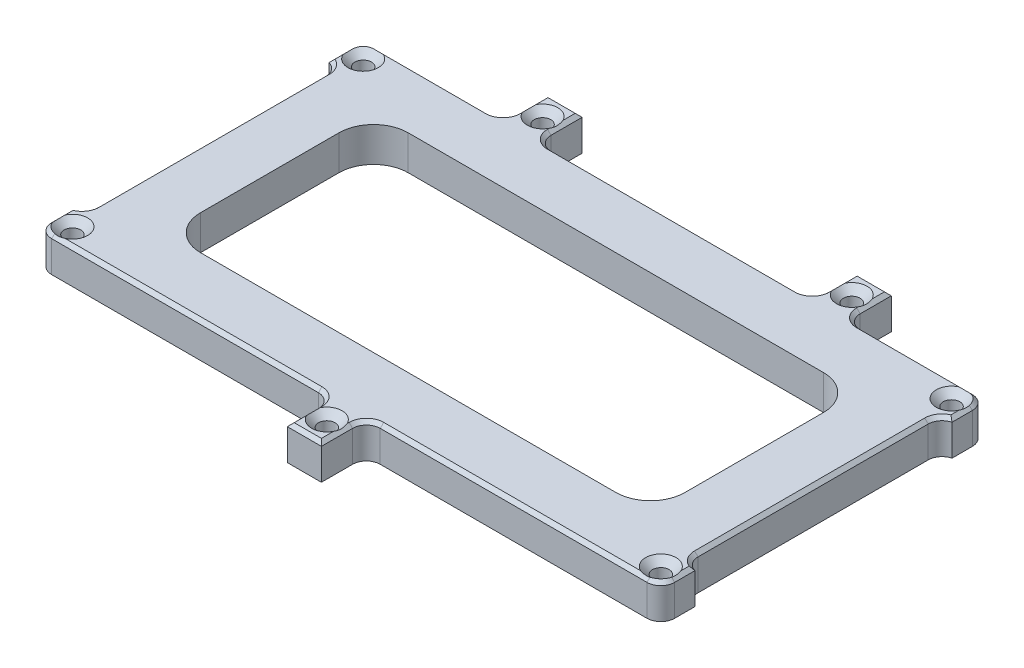
SolidWorks part; units mm, degrees
material "ABS"
ref_plane "Front Plane" through (0, 0, 0) normal (0, 0, 1) x (1, 0, 0)
ref_plane "Top Plane" through (0, 0, 0) normal (0, 1, 0) x (1, 0, 0)
ref_plane "Right Plane" through (0, 0, 0) normal (1, 0, 0) x (0, 0, -1)
sketch "Sketch1" plane through (0, 0, 0) normal (0, 1, 0) x (1, 0, 0)
  line L0 (-45, -23.5) -> (-45, -18.565)
  line L5 (-45, -23.5) -> (45, -23.5) construction
  line L6 (-45, -23.5) -> (-45, 23.5) construction
  line L7 (-45, 23.5) -> (45, 23.5) construction
  line L8 (45, -23.5) -> (45, 23.5) construction
  line L9 (-45, -23.5) -> (45, 23.5) construction
  line L10 (-45, 23.5) -> (45, -23.5) construction
  line L11 (-45, -18.565) -> (-43.5, -18.565)
  line L12 (-43.5, -18.565) -> (-43.5, 18.565)
  line L13 (-43.5, 18.565) -> (-45, 18.565)
  line L14 (-45, 18.565) -> (-45, 23.5)
  line L15 (-45, 23.5) -> (-24.8, 23.5)
  line L16 (-24.8, 23.5) -> (-24.8, 30)
  line L17 (-24.8, 30) -> (-19.87, 30)
  line L18 (-19.87, 30) -> (-19.87, 23.5)
  line L19 (-19.87, 23.5) -> (19.87, 23.5)
  line L20 (19.87, 23.5) -> (19.87, 30)
  line L21 (19.87, 30) -> (24.8, 30)
  line L22 (24.8, 30) -> (24.8, 23.5)
  line L23 (24.8, 23.5) -> (45, 23.5)
  line L24 (45, 23.5) -> (45, 18.565)
  line L25 (45, 18.565) -> (43.5, 18.565)
  line L26 (43.5, 18.565) -> (43.5, -18.565)
  line L27 (43.5, -18.565) -> (45, -18.565)
  line L28 (45, -18.565) -> (45, -23.5)
  line L29 (45, -23.5) -> (2.465, -23.5)
  line L30 (2.465, -23.5) -> (2.465, -30)
  line L31 (2.465, -30) -> (-2.465, -30)
  line L32 (-2.465, -30) -> (-2.465, -23.5)
  line L33 (-2.465, -23.5) -> (-45, -23.5)
  point P0 (0, 0)
  dimension "D1" = 47
  dimension "D2" = 90
  dimension "D3" = 87
  dimension "D4" = 60
  dimension "D5" = 20.2
  dimension "D6" = 4.93
  dimension "D7" = 37.13
extrude "Boss-Extrude1" add sketch "Sketch1" along normal blind 5
hole_wizard "CSK for M2 Countersunk Flat Head Screw1" positions "Sketch2" profile "Sketch3" countersink size "M2" standard "DIN" end condition up to next
sketch "Sketch2" plane through (0, 5, 0) normal (0, 1, 0) x (1, 0, 0)
  line L0 (-19.87, 30) -> (-24.8, 30) construction
  line L1 (24.8, 30) -> (19.87, 30) construction
  line L2 (-2.465, -30) -> (2.465, -30) construction
  line L3 (-24.8, 30) -> (-24.8, 23.5) construction
  line L4 (-2.465, -23.5) -> (-2.465, -30) construction
  point P0 (0, -26.75)
  point P2 (22.335, 26.75)
  point P4 (-22.335, 26.75)
  point P11 (-22.335, 30)
  point P15 (22.335, 30)
  point P19 (0, -30)
  point P24 (-24.8, 26.75)
  point P28 (-2.465, -26.75)
  point P29 (-42.5, 21)
  point P31 (-42.5, -21)
  point P33 (42.5, 21)
  point P35 (42.5, -21)
  dimension "D1" = 21
  dimension "D2" = 21
  dimension "D3" = 42.5
  dimension "D4" = 42.5
sketch "Sketch3" plane through (0, 5, 26.75) normal (1, 0, 0) x (0, 0, 1)
  line L0 (0, 0) -> (0, 5)
  line L1 (0, 5) -> (1.2, 5)
  line L2 (1.2, 5) -> (1.2, 1)
  line L3 (1.2, 1) -> (2.2, 0)
  line L5 (2.2, 0) -> (0, 0)
  line L6 (-1.2, 1) -> (-2.2, 0) construction
  line L11 (0, -6.35) -> (0, 107.95) construction
  dimension "Thru Hole Dia." = 2.4
  dimension "Thru Hole Depth" = 5
  dimension "Near C'Sink Dia." = 4.4
  dimension "Near C'Sink Angle" = 90
fillet "Fillet2" radius 2 14 edges at (-2.465, 2.5, 23.5) (-45, 2.5, 23.5) (-43.5, 2.5, 18.565) (-43.5, 2.5, -18.565) (-45, 2.5, -23.5) (-24.8, 2.5, -23.5) (-19.87, 2.5, -23.5) (19.87, 2.5, -23.5) (24.8, 2.5, -23.5) (43.5, 2.5, -18.565) (45, 2.5, -23.5) (45, 2.5, 23.5) (43.5, 2.5, 18.565) (2.465, 2.5, 23.5)
chamfer "Chamfer2" distance 0.5 angle 45 34 edges at (-22.335, 5, -30) (22.335, 5, -30) (19.87, 5, -27.75) (-19.87, 5, -27.75) (19.2842, 5, -24.0858) (-19.2842, 5, -24.0858) (0, 5, -23.5) (45, 5, -20.0325) (24.8, 5, -27.75) (44.4142, 5, -22.9142) (25.3858, 5, -24.0858) (34.9, 5, -23.5) (43.9189, 5, 17.8533) (43.9189, 5, -17.8533) (43.5, 5, 0) (45, 5, 20.0325) (44.4142, 5, 22.9142) (23.7325, 5, 23.5) (3.0508, 5, 24.0858) (2.465, 5, 27.75) (0, 5, 30) (-2.465, 5, 27.75) (-3.0508, 5, 24.0858) (-23.7325, 5, 23.5) (-44.4142, 5, 22.9142) (-45, 5, 20.0325) (-24.8, 5, -27.75) (-25.3858, 5, -24.0858) (-34.9, 5, -23.5) (-44.4142, 5, -22.9142) (-45, 5, -20.0325) (-43.9189, 5, -17.8533) (-43.9189, 5, 17.8533) (-43.5, 5, 0)
sketch "Sketch4" plane through (0, 5, 0) normal (0, 1, 0) x (1, 0, 0)
  line L1 (-35, -15) -> (35, -15)
  line L2 (-35, -15) -> (-35, 15)
  line L3 (-35, 15) -> (35, 15)
  line L4 (35, -15) -> (35, 15)
  line L5 (-35, -15) -> (35, 15) construction
  line L6 (-35, 15) -> (35, -15) construction
  point P0 (0, 0)
  dimension "D1" = 30
  dimension "D2" = 70
extrude "Cut-Extrude1" cut sketch "Sketch4" against normal up to next
fillet "Fillet3" radius 5 4 edges at (35, 2.5, 15) (-35, 2.5, 15) (35, 2.5, -15) (-35, 2.5, -15)
